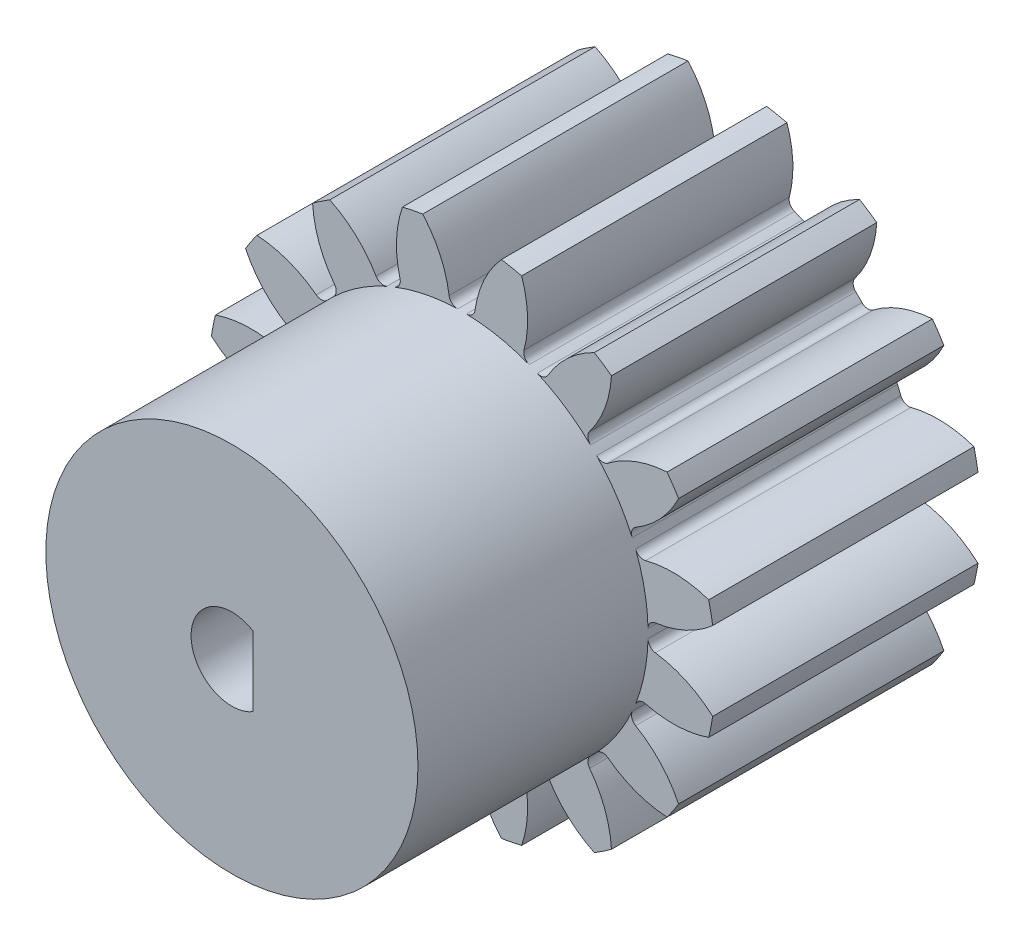
SolidWorks part; units mm, degrees
material "Cast Alloy Steel"
ref_plane "Front Plane" through (0, 0, 0) normal (0, 0, 1) x (1, 0, 0)
ref_plane "Top Plane" through (0, 0, 0) normal (0, 1, 0) x (1, 0, 0)
ref_plane "Right Plane" through (0, 0, 0) normal (1, 0, 0) x (0, 0, -1)
sketch "Sketch1" plane through (0, 0, 0) normal (0, 0, 1) x (1, 0, 0)
  line L0 (0.6, -0.9811) -> (0.6, 0.9811)
  circle A0 centre (0, 0) radius 6.3504
  circle A1 centre (0, 0) radius 7.1442
  circle A2 centre (0, 0) radius 5.2391
  circle A3 centre (0, 0) radius 1.15
  dimension "D1" = 12.7008
  dimension "D2" = 14.2884
  dimension "D4" = 2.3
  dimension "D3" = 1.9051
  dimension "D5" = 0.6
extrude "Boss-Extrude2" add sketch "Sketch1" along normal blind 7.47 contours A1
sketch "Sketch4" plane through (0, 0, 7.47) normal (0, 0, 1) x (1, 0, 0)
  line L0 (0, 0) -> (0, 7.1442) construction
  line L1 (0.6224, 6.3198) -> (-0.6224, 6.3198) construction
  line L2 (0, 0) -> (0.3426, 5.2279) construction
  line L3 (0, 4.985) -> (1.4154, 8.0203) construction
  line L4 (0, 0) -> (-1.3938, 7.0069) construction
  line L5 (-0.6224, 6.3198) -> (-1.8434, 6.077) construction
  circle A0 centre (0, 0) radius 7.1442 construction
  arc A1 (0.3426, 5.2279) -> (2.1986, 7.8418) centre (3.3928, 5.028) cw
  arc A2 (-0.3426, 5.2279) -> (-2.1986, 7.8418) centre (-3.3928, 5.028) ccw
  circle A3 centre (0, 0) radius 5.2391 construction
  arc A4 (0.3426, 5.2279) -> (-0.3426, 5.2279) centre (0, 0) ccw
  circle A6 centre (0, 0) radius 6.3504 construction
  circle A7 centre (0, 0) radius 7.1442 construction
  circle A10 centre (0, 0) radius 8.1442
  arc A11 (2.1986, 7.8418) -> (-2.1986, 7.8418) centre (0, 0) ccw
  dimension "D2" = 25
  dimension "D3" = 11.25
extrude "Cut-Extrude1" cut sketch "Sketch4" against normal through all both and the other way through all
fillet "Fillet1" radius 0.2381 2 edges at (-0.3426, 5.2279, 3.735) (0.3426, 5.2279, 3.735)
pattern_circular "CirPattern2" count 16 over 360 about axis through (0, 0, 7.47) along (0, 0, -1) of "Cut-Extrude1", "Fillet1" reverse direction yes
extrude "Boss-Extrude3" add sketch "Sketch1<6>" along normal blind 13.95 contours A2
sketch "Sketch1<6>" plane through (0, 0, 0) normal (0, 0, 1) x (1, 0, 0) same geometry as "Sketch1"
extrude "Cut-Extrude4" cut sketch "Sketch1<5>" against normal through all and the other way through all contours L0 A3 region at (-0.1856, 0, 0)
sketch "Sketch1<5>" plane through (0, 0, 0) normal (0, 0, 1) x (1, 0, 0) same geometry as "Sketch1"
ref_plane "Plane1" through (0, 0, 7.47) normal (0, 0, 1) x (1, 0, 0)
sketch "Sketch5" plane through (0, 0, 7.47) normal (0, 0, 1) x (1, 0, 0)
  circle A0 centre (0, 0) radius 7.1442 construction
  circle A1 centre (0, 0) radius 7.1442
equation "\"Module\"= 0.7938"
equation "\"Numer of theeth\"= 16"
equation "\"D1@Sketch1\"=\"Module\" * \"Numer of theeth\""
equation "\"D2@Sketch1\"=(\"Numer of theeth\" + 2) * \"Module\""
equation "\"D3@Sketch1\"=\"Module\" * if( \"Module\" =>1.25,2.25,2.4)"
equation "\"pressure angle\"= 25deg"
equation "\"D2@Sketch4\"=\"pressure angle\""
equation "\"D3@Sketch4\"=180 / \"Numer of theeth\""
equation "\"D1@Fillet1\"=.3 * \"Module\""
equation "\"D1@CirPattern2\"=\"Numer of theeth\""
